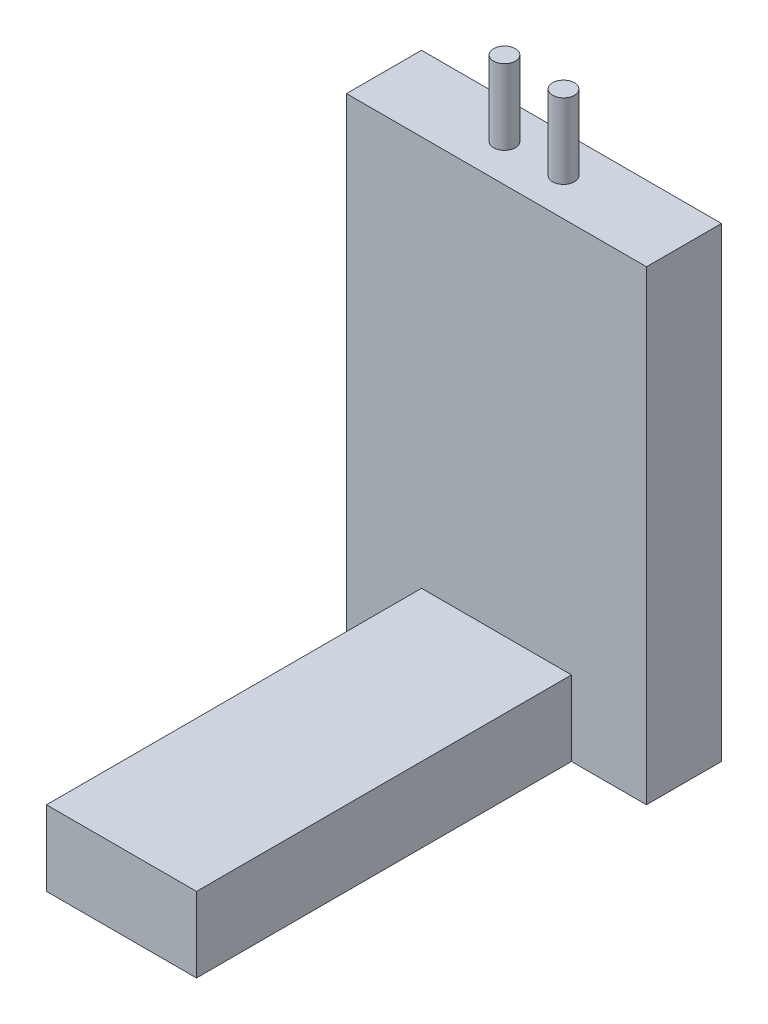
SolidWorks part; units mm, degrees
ref_plane "Front Plane" through (0, 0, 0) normal (0, 0, 1) x (1, 0, 0)
ref_plane "Top Plane" through (0, 0, 0) normal (0, 1, 0) x (1, 0, 0)
ref_plane "Right Plane" through (0, 0, 0) normal (1, 0, 0) x (0, 0, -1)
sketch "Sketch3" plane through (0, 0, 0) normal (0, 1, 0) x (1, 0, 0)
  line L0 (-25.4, 0) -> (76.2, 0)
  line L1 (-25.4, 0) -> (-25.4, 25.4)
  line L2 (-25.4, 25.4) -> (76.2, 25.4)
  line L3 (76.2, 25.4) -> (76.2, 0)
extrude "Boss-Extrude1" add sketch "Sketch3" along normal blind 157.8
sketch "Sketch6" plane through (0, 157.8, 0) normal (0, 1, 0) x (1, 0, 0)
  line L0 (25.4, 25.4) -> (25.4, 0) construction
  line L1 (76.2, 25.4) -> (-25.4, 25.4) construction
  line L2 (-25.4, 0) -> (76.2, 0) construction
  line L3 (25.4, 12.7) -> (15.4, 12.7) construction
  line L5 (25.4, 12.7) -> (35.4, 12.7) construction
  circle A0 centre (15.4, 12.7) radius 3.683
  circle A2 centre (35.4, 12.7) radius 3.683
  dimension "D1" = 7.366
  dimension "D2" = 7.366
extrude "Boss-Extrude4" add sketch "Sketch6" along normal blind 25.4
sketch "Sketch7" plane through (0, 0, 0) normal (0, -1, 0) x (-1, 0, 0)
  line L0 (-25.4, 12.7) -> (5.08, 12.7) construction
  line L2 (-25.4, 25.4) -> (-25.4, 12.7) construction
  line L3 (-25.4, 12.7) -> (-55.88, 12.7) construction
  line L4 (-76.2, 25.4) -> (25.4, 25.4) construction
  circle A1 centre (5.08, 12.7) radius 5.207
  circle A2 centre (-55.88, 12.7) radius 5.207
  dimension "D1" = 10.414
  dimension "D2" = 10.414
extrude "Cut-Extrude1" cut sketch "Sketch7" against normal blind 17.78
sketch "Sketch8" plane through (0, 0, 0) normal (0, 0, 1) x (1, 0, 0)
  line L0 (25.4, 0) -> (25.4, 25.4) construction
  line L1 (-25.4, 0) -> (76.2, 0) construction
  line L2 (25.4, 25.4) -> (50.8, 25.4) construction
  line L3 (25.4, 25.4) -> (0, 25.4) construction
  line L5 (0, 25.4) -> (50.8, 25.4)
  line L6 (0, 25.4) -> (0, 0)
  line L7 (0, 0) -> (50.8, 0)
  line L8 (50.8, 25.4) -> (50.8, 0)
extrude "Boss-Extrude5" add sketch "Sketch8" along normal blind 127
